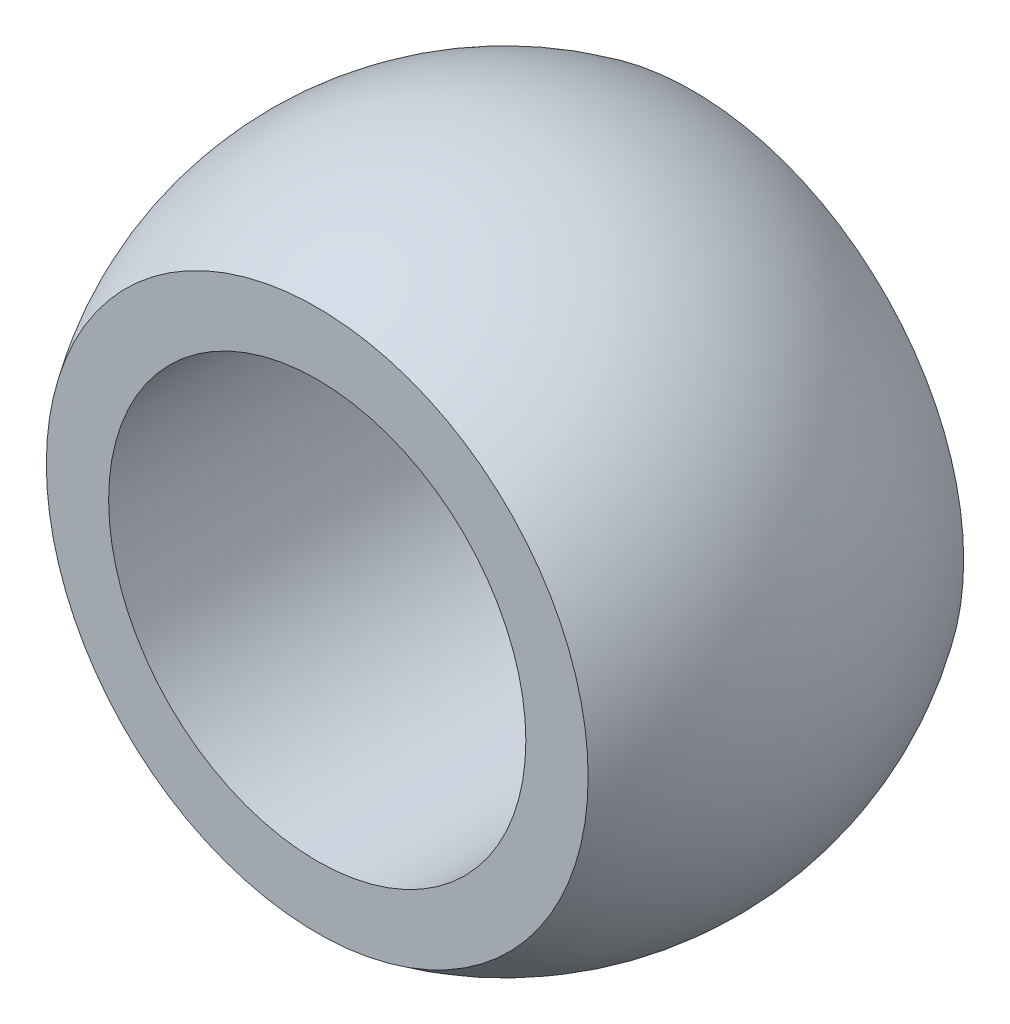
SolidWorks part; units mm, degrees
ref_plane "前视基准面" through (0, 0, 0) normal (0, 0, 1) x (1, 0, 0)
ref_plane "上视基准面" through (0, 0, 0) normal (0, 1, 0) x (1, 0, 0)
ref_plane "右视基准面" through (0, 0, 0) normal (1, 0, 0) x (0, 0, -1)
other "Configuration Table"
sketch "草图1" plane through (0, 0, 0) normal (0, 1, 0) x (1, 0, 0)
  line L0 (-7.9, 0) -> (7.9, 0)
  circle A0 centre (0, 0) radius 7.9
  dimension "D1" = 15.8
revolve "旋转1" add sketch "草图1" angle 360 about L0 region at (0, 0, -3.3529)
sketch "草图2" plane through (0, 0, 0) normal (0, 1, 0) x (1, 0, 0)
  line L1 (-11.0368, 4.5) -> (10.2474, 4.5)
  line L2 (-11.0368, 4.5) -> (-11.0368, -4.5)
  line L3 (-11.0368, -4.5) -> (10.2474, -4.5)
  line L4 (10.2474, 4.5) -> (10.2474, -4.5)
  point P4 (-11.0368, 0)
  point P6 (10.2474, 0)
  dimension "D1" = 9
extrude "切除-拉伸1" cut sketch "草图2" against normal blind 10 and the other way blind 10 flip side to cut
sketch "草图3" plane through (0, 0, -4.5) normal (0, 0, -1) x (-1, 0, 0)
  circle A0 centre (0, 0) radius 5
  dimension "D1" = 10
extrude "切除-拉伸2" cut sketch "草图3" against normal blind 10
